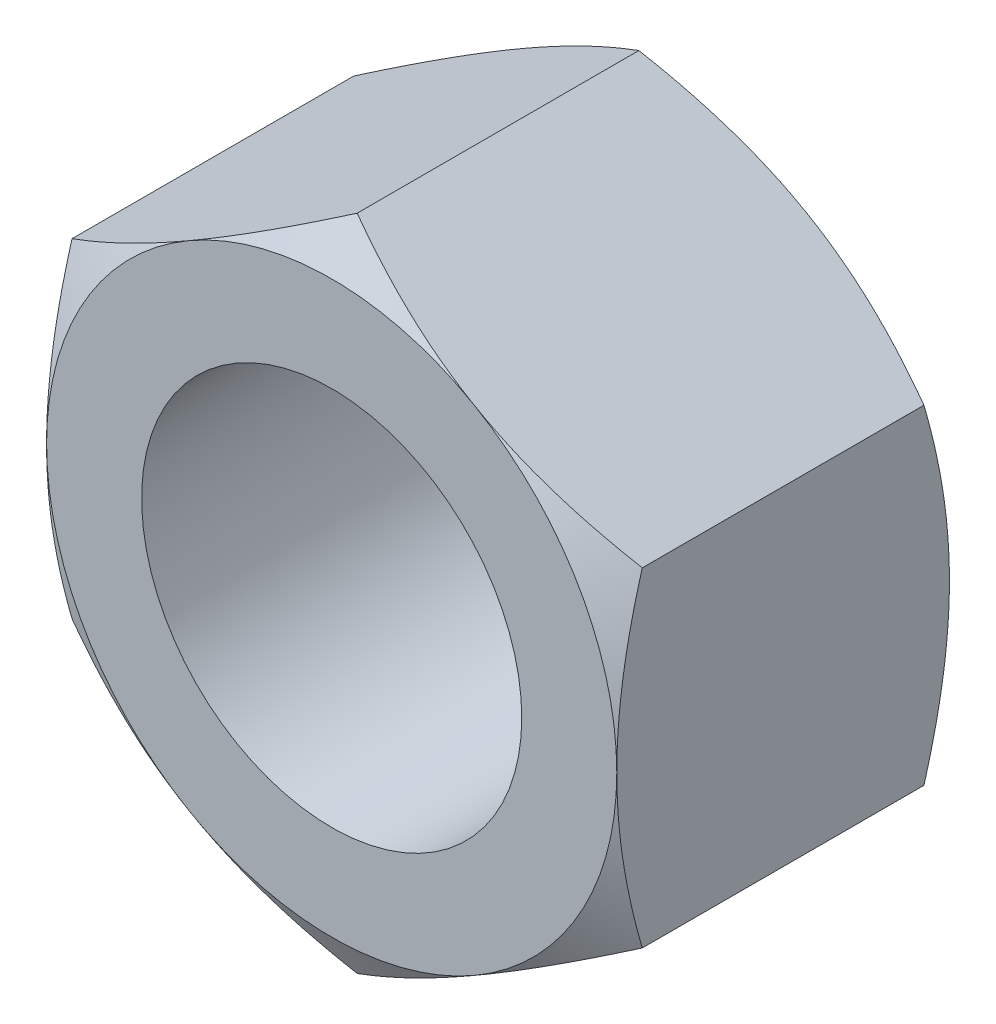
SolidWorks part; units mm, degrees
material "Plain Carbon Steel"
ref_plane "Front" through (0, 0, 0) normal (0, 0, 1) x (1, 0, 0)
ref_plane "Top" through (0, 0, 0) normal (0, 1, 0) x (1, 0, 0)
ref_plane "Right" through (0, 0, 0) normal (1, 0, 0) x (0, 0, -1)
sketch "Sketch1" plane through (0, 0, 0) normal (0, 0, 1) x (1, 0, 0)
  line L1 (-11.9062, 6.8741) -> (-11.9062, -6.8741)
  line L2 (-11.9062, -6.8741) -> (0, -13.7482)
  line L3 (0, -13.7482) -> (11.9063, -6.8741)
  line L4 (11.9063, -6.8741) -> (11.9063, 6.8741)
  line L5 (11.9063, 6.8741) -> (0, 13.7482)
  line L6 (0, 13.7482) -> (-11.9062, 6.8741)
  circle A0 centre (0, 0) radius 11.9062 construction
  circle A1 centre (0, 0) radius 7.9375
  point P10 (0, 7.9375)
  dimension "hex" = 23.8125
  dimension "dia" = 15.875
extrude "Extrude1" add sketch "Sketch1" along normal mid plane 13.8906
sketch "Sketch4" plane through (0, 0, -6.9453) normal (0, 0, -1) x (-1, 0, 0)
  circle A0 centre (0, 0) radius 7.9375 construction
  circle A1 centre (0, 0) radius 7.9375
curve "Helix/Spiral3" [suppressed] pitch 2.3091 height 16.6687 turns 7.2188
sketch "Sketch3" plane through (0, 0, 0) normal (1, 0, 0) x (0, 0, -1)
  line L0 (6.9453, 7.9375) -> (8.9658, 7.9375)
  line L1 (8.9658, 7.9375) -> (8.0999, 6.4377)
  line L2 (8.0999, 6.4377) -> (7.8112, 6.4377)
  line L3 (7.8112, 6.4377) -> (6.9453, 7.9375)
  line L4 (7.3783, 7.1876) -> (8.5328, 7.1876) construction
  dimension "D1" = 60
  dimension "D2" = 1.1545
  dimension "D3" = 0.2886
sweep "Sweep1" [suppressed] add profiles "Sketch3" path "Helix/Spiral3"
sketch "Sketch6" [suppressed] plane through (0, 0, 0) normal (1, 0, 0) x (0, 0, -1)
  line L0 (-7.5226, 8.5148) -> (-6.368, 7.3602)
  line L1 (-6.368, 7.3602) -> (-6.368, 0) construction
  line L2 (9.6446, 0) -> (-9.6446, 0) construction
  line L3 (-6.368, 0) -> (-9.7227, 0)
  line L4 (-9.7227, 0) -> (-9.7227, 8.5148)
  line L5 (-9.7227, 8.5148) -> (-7.5226, 8.5148)
  line L6 (-6.368, 7.3602) -> (0.9922, 0)
  line L7 (0.9922, 0) -> (-6.368, 0)
  line L8 (-6.9453, -6.8741) -> (-6.9453, 6.8741) construction
  point P2 (-6.9453, 7.9375)
  dimension "D2" = 1.1545
  dimension "D1" = 45
revolve "Cut-Revolve1" [suppressed] cut sketch "Sketch6" angle 360 about L3
sketch "Sketch7" plane through (0, 0, 6.9453) normal (0, 0, 1) x (1, 0, 0)
  circle A0 centre (0, 0) radius 11.9062 construction
  circle A1 centre (0, 0) radius 11.9062
extrude "Extrude2" cut sketch "Sketch7" against normal blind 25.4 draft 60 flip side to cut
mirror "Mirror1" about plane through (0, 0, 0) normal (0, 0, 1) of "Extrude2", "Cut-Revolve1"
sketch "Sketch8" [suppressed] plane through (0, 0, 6.9453) normal (0, 0, 1) x (1, 0, 0)
  line L0 (-5.6127, 5.6127) -> (0, 0) construction
  line L1 (0, -9.6446) -> (0, 9.6446) construction
  circle A0 centre (0, 0) radius 7.9375 construction
  point P0 (-5.6127, 5.6127)
  dimension "D1" = 45
equation "\"D3@Helix/Spiral3\" = \"length@Extrude1\" * 1.2"
equation "\"D2@Sketch3\" = \"D4@Helix/Spiral3\" * .5"
equation "\"D3@Sketch3\" = \"D4@Helix/Spiral3\" * .125"
equation "\"D2@Sketch6\" = \"D4@Helix/Spiral3\" * .5"
